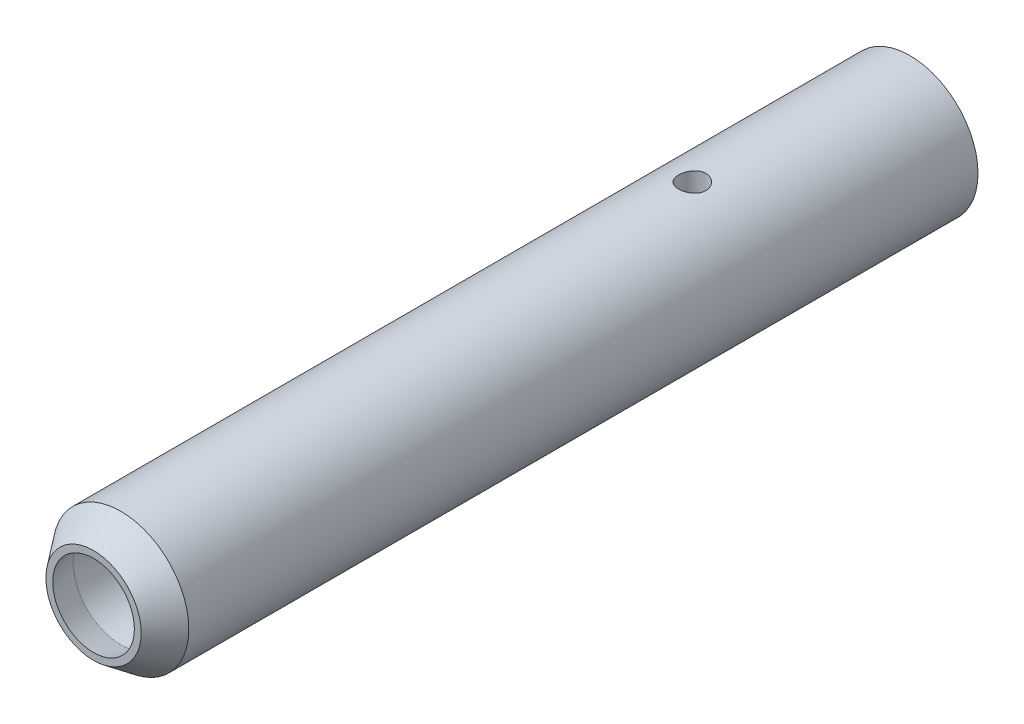
SolidWorks part; units mm, degrees
material "1060 Alloy"
ref_plane "Front Plane" through (0, 0, 0) normal (0, 0, 1) x (1, 0, 0)
ref_plane "Top Plane" through (0, 0, 0) normal (0, 1, 0) x (1, 0, 0)
ref_plane "Right Plane" through (0, 0, 0) normal (1, 0, 0) x (0, 0, -1)
sketch "Sketch1" plane through (0, 0, 0) normal (0, 0, 1) x (1, 0, 0)
  circle A0 centre (0, 0) radius 6.35
  circle A1 centre (0, 0) radius 3.175
  dimension "D1" = 12.7
  dimension "D2" = 6.35
extrude "Boss-Extrude1" add sketch "Sketch1" along normal mid plane 50.8
ref_plane "Plane1" through (0, 0, -10.16) normal (0, 0, -1) x (-1, 0, 0)
sketch "Sketch2" plane through (0, 0, -10.16) normal (0, 0, -1) x (-1, 0, 0)
  circle A0 centre (0, 0) radius 6.35
  dimension "D1" = 12.7
extrude "Boss-Extrude2" add sketch "Sketch2" against normal blind 7.62
ref_plane "Plane2" through (0, 6.35, 0) normal (0, 1, 0) x (1, 0, 0)
sketch "Sketch3" plane through (0, 6.35, 0) normal (0, 1, 0) x (1, 0, 0)
  circle A0 centre (0, 5.08) radius 1.27
  point P3 (0, 0)
  point P4 (0, -6.3819)
  dimension "D1" = 2.54
  dimension "D2" = 5.08
sketch "Sketch4" plane through (0, 0, 25.4) normal (0, 0, 1) x (1, 0, 0)
  circle A0 centre (0, 0) radius 4.445
  dimension "D1" = 8.89
extrude "Cut-Extrude2" cut sketch "Sketch4" against normal up to surface (27.94 mm away) up to face at (-3.175, 0, -2.54)
sketch "Sketch6" plane through (0, 0, 25.4) normal (0, 0, 1) x (1, 0, 0)
  circle A0 centre (0, 0) radius 6.35
  circle A1 centre (0, 0) radius 4.445
  dimension "D1" = 12.7
  dimension "D2" = 8.89
extrude "Boss-Extrude4" add sketch "Sketch6" along normal blind 22.86
sketch "Sketch8" plane through (0, 0, 48.26) normal (0, 0, 1) x (1, 0, 0)
  circle A0 centre (0, 0) radius 6.35
  circle A1 centre (0, 0) radius 4.445
  dimension "D1" = 12.7
  dimension "D2" = 8.89
ref_plane "Plane3" through (0, 0, 50.8) normal (0, 0, 1) x (1, 0, 0)
sketch "Sketch9" plane through (0, 0, 50.8) normal (0, 0, 1) x (1, 0, 0)
  circle A0 centre (0, 0) radius 4.445
  circle A1 centre (0, 0) radius 3.81
  dimension "D1" = 8.89
  dimension "D2" = 7.62
loft "Loft1" add section "Sketch8" section "Sketch9" connector at (6.0179, 2.0267, 48.26) connector at (3.9208, 2.0941, 50.8)
loft "Cut-Loft1" cut section "Sketch8<7>" section "Sketch9<7>" connector at (3.9819, 1.9756, 48.26) connector at (3.3778, 1.7625, 50.8)
sketch "Sketch8<7>" plane through (0, 0, 48.26) normal (0, 0, 1) x (1, 0, 0) same geometry as "Sketch8"
sketch "Sketch9<7>" plane through (0, 0, 50.8) normal (0, 0, 1) x (1, 0, 0) same geometry as "Sketch9"
ref_plane "Plane4" through (0, 0, -2.54) normal (0, 0, -1) x (-1, 0, 0)
sketch "Sketch10" plane through (0, 0, -2.54) normal (0, 0, -1) x (-1, 0, 0)
  circle A0 centre (0, 0) radius 1.27
  dimension "D1" = 2.54
sketch "Sketch12" plane through (0, 0, 0) normal (1, 0, 0) x (0, 0, -1)
  line L0 (2.54, 0) -> (3.81, 0)
  line L2 (2.54, -1.27) -> (2.54, 1.27) construction
  line L3 (5.08, 1.27) -> (5.08, 6.35)
  line L4 (6.35, 6.35) -> (3.81, 6.35) construction
  arc A0 (5.08, 1.27) -> (3.81, 0) centre (3.81, 1.27) cw
  dimension "D1" = 1.27
sweep "Cut-Sweep1" cut profiles "Sketch3" path "Sketch12"
